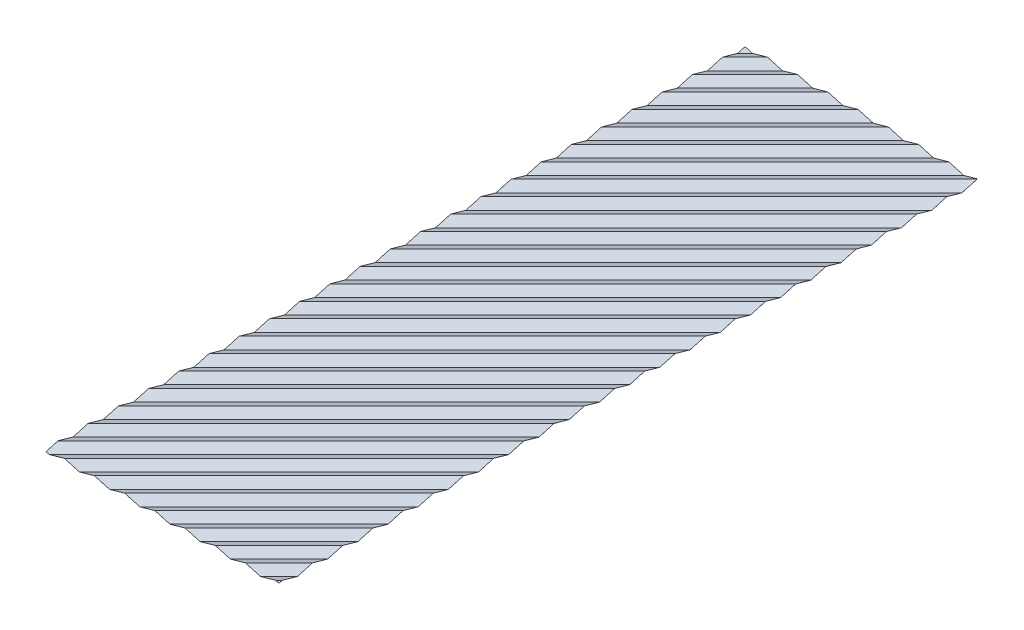
SolidWorks part; units mm, degrees
material "solkoted Mesh"
ref_plane "Front Plane" through (0, 0, 0) normal (0, 0, 1) x (1, 0, 0)
ref_plane "Top Plane" through (0, 0, 0) normal (0, 1, 0) x (1, 0, 0)
ref_plane "Right Plane" through (0, 0, 0) normal (1, 0, 0) x (0, 0, -1)
ref_axis "Axis1" through (0, -55, 0) along (0, 1, 0)
ref_plane "Plane1" through (0, 0, 0) normal (0.7071, 0, -0.7071) x (-0.7071, 0, -0.7071)
sketch "Sketch1" plane through (0, 0, 0) normal (0.7071, 0, -0.7071) x (-0.7071, 0, -0.7071)
  line L0 (-869.95, 5.588) -> (-855.98, 11.176)
  line L1 (-855.98, 11.176) -> (-842.01, 5.588)
  line L2 (-842.01, 5.588) -> (-869.95, 5.588) construction
  line L3 (-855.98, 11.176) -> (-855.98, 5.588) construction
  line L4 (-842.01, 5.588) -> (-828.04, 0)
  line L5 (-828.04, 0) -> (-814.07, 5.588)
  line L6 (-828.04, 0) -> (-828.04, 5.588) construction
  line L7 (-814.07, 5.588) -> (-842.01, 5.588) construction
  line L8 (-828.04, 0) -> (0, 0) construction
  point P8 (-828.04, 5.588)
  dimension "D1" = 869.95
  dimension "D2" = 27.94
  dimension "D3" = 5.588
extrude "Extrude-Thin1" add sketch "Sketch1" along normal mid plane 2411.184 thin thin type mid plane wall 0.0508
ref_axis "Axis2" through (-62.9254, 0, -62.9254) along (0.7071, 0, 0.7071)
pattern_linear "LPattern1" count 31 spacing 55.88 along (-0.7071, 0, -0.7071) of "Extrude-Thin1"
sketch "Sketch2" plane through (0, 0, 0) normal (0, 1, 0) x (1, 0, 0)
  line L1 (304.8, -914.4) -> (-304.8, -914.4)
  line L2 (304.8, -914.4) -> (304.8, 914.4)
  line L3 (304.8, 914.4) -> (-304.8, 914.4)
  line L4 (-304.8, -914.4) -> (-304.8, 914.4)
  line L5 (304.8, -914.4) -> (-304.8, 914.4) construction
  line L6 (304.8, 914.4) -> (-304.8, -914.4) construction
  point P0 (0, 0)
  dimension "D1" = 1828.8
  dimension "D2" = 609.6
extrude "Cut-Extrude1" cut sketch "Sketch2" against normal through all both and the other way through all flip side to cut
